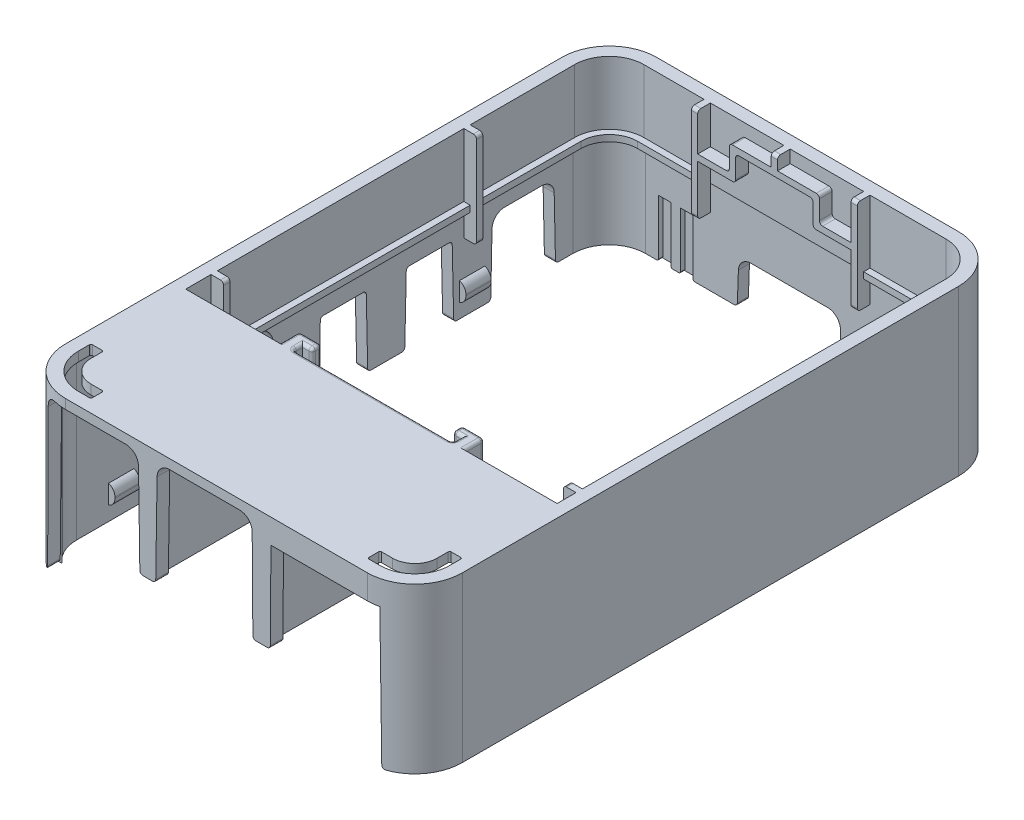
SolidWorks part; units mm, degrees
ref_plane "Plan de face" through (0, 0, 0) normal (0, 0, 1) x (1, 0, 0)
ref_plane "Plan de dessus" through (0, 0, 0) normal (0, 1, 0) x (1, 0, 0)
ref_plane "Plan de droite" through (0, 0, 0) normal (1, 0, 0) x (0, 0, -1)
sketch "Esquisse1" plane through (0, 0, 0) normal (0, 1, 0) x (1, 0, 0)
  line L1 (-31.375, 46.75) -> (31.375, 46.75)
  line L2 (-31.375, 46.75) -> (-31.375, -46.75)
  line L3 (-31.375, -46.75) -> (31.375, -46.75)
  line L4 (31.375, 46.75) -> (31.375, -46.75)
  line L5 (-31.375, 46.75) -> (31.375, -46.75) construction
  line L6 (-31.375, -46.75) -> (31.375, 46.75) construction
  point P0 (0, 0)
  dimension "D1" = 62.75
  dimension "D2" = 93.5
extrude "Contour_de_matiere" add sketch "Esquisse1" along normal blind 26
fillet "Arrondissement_des_coins" radius 7.5 4 edges at (-31.375, 13, -46.75) (31.375, 13, -46.75) (31.375, 13, 46.75) (-31.375, 13, 46.75)
sketch "Esquisse2" plane through (0, 26, 0) normal (0, 1, 0) x (1, 0, 0)
  line L0 (-29.375, -22.25) -> (29.375, -22.25)
  line L4 (-23.875, -46.75) -> (23.875, -46.75) construction
  line L8 (-23.875, 44.75) -> (23.875, 44.75)
  line L9 (-29.375, 39.25) -> (-29.375, -22.25)
  line L10 (29.375, 39.25) -> (29.375, -22.25)
  line L11 (31.375, -39.25) -> (31.375, 39.25) construction
  line L12 (-31.375, 39.25) -> (-31.375, -39.25) construction
  line L13 (23.875, 46.75) -> (-23.875, 46.75) construction
  arc A2 (-29.375, 39.25) -> (-23.875, 44.75) centre (-23.875, 39.25) cw
  arc A3 (23.875, 44.75) -> (29.375, 39.25) centre (23.875, 39.25) cw
  dimension "D4" = 24.5
  dimension "D5" = 5.5
  dimension "D6" = 5.5
  dimension "D1" = 2
  dimension "D2" = 2
  dimension "D3" = 2
extrude "Creusage_du_trou_central" cut sketch "Esquisse2" against normal up to next
ref_plane "Plan_pour_rebord_interieur" through (0, 15, 0) normal (0, 1, 0) x (1, 0, 0)
sketch "Esquisse4" plane through (0, 15, 0) normal (0, 1, 0) x (1, 0, 0)
  line L0 (-28.375, -22.25) -> (-31.375, -22.25)
  line L1 (-29.375, -22.25) -> (29.375, -22.25) construction
  line L2 (-31.375, 39.25) -> (-31.375, -39.25) construction
  line L3 (-31.375, -22.25) -> (-31.375, 39.25)
  line L4 (-23.875, 46.75) -> (23.875, 46.75)
  line L5 (31.375, 39.25) -> (31.375, -22.25)
  line L6 (31.375, -39.25) -> (31.375, 39.25) construction
  line L7 (31.375, -22.25) -> (28.375, -22.25)
  line L8 (28.375, -22.25) -> (28.375, 39.25)
  line L9 (-28.375, -22.25) -> (-28.375, 39.25)
  line L10 (-23.875, 43.75) -> (23.875, 43.75)
  line L11 (-29.375, 39.25) -> (-29.375, -22.25) construction
  line L12 (29.375, -22.25) -> (29.375, 39.25) construction
  line L13 (23.875, 44.75) -> (-23.875, 44.75) construction
  arc A0 (-31.375, 39.25) -> (-23.875, 46.75) centre (-23.875, 39.25) cw
  arc A1 (23.875, 46.75) -> (31.375, 39.25) centre (23.875, 39.25) cw
  arc A2 (-28.375, 39.25) -> (-23.875, 43.75) centre (-23.875, 39.25) cw
  arc A3 (23.875, 43.75) -> (28.375, 39.25) centre (23.875, 39.25) cw
  dimension "D4" = 4.5
  dimension "D5" = 4.5
  dimension "D1" = 1
  dimension "D2" = 1
  dimension "D3" = 1
extrude "Rebord_interieux" add sketch "Esquisse4" along normal blind 1
sketch "Esquisse5" plane through (0, 26, 0) normal (0, 1, 0) x (1, 0, 0)
  line L0 (-31.375, 39.25) -> (-31.375, -39.25) construction
  line L1 (-31.375, -18.25) -> (-27.375, -18.25)
  line L2 (-31.375, -18.25) -> (-31.375, -17.25)
  line L3 (-31.375, -17.25) -> (-27.375, -17.25)
  line L4 (-27.375, -18.25) -> (-27.375, -17.25)
  line L5 (-31.375, -18.25) -> (-27.375, -17.25) construction
  line L6 (-31.375, -17.25) -> (-27.375, -18.25) construction
  line L7 (23.875, 46.75) -> (-23.875, 46.75) construction
  line L8 (31.375, -39.25) -> (31.375, 39.25) construction
  line L9 (31.375, -19.25) -> (27.375, -19.25)
  line L10 (31.375, -19.25) -> (31.375, -18.25)
  line L11 (31.375, -18.25) -> (27.375, -18.25)
  line L12 (27.375, -19.25) -> (27.375, -18.25)
  line L13 (31.375, -19.25) -> (27.375, -18.25) construction
  line L14 (31.375, -18.25) -> (27.375, -19.25) construction
  line L15 (10.875, 46.75) -> (11.875, 46.75)
  line L16 (-29.375, -22.25) -> (29.375, -22.25) construction
  line L17 (-31.375, 21.75) -> (-27.375, 21.75)
  line L18 (-31.375, 21.75) -> (-31.375, 22.75)
  line L19 (-31.375, 22.75) -> (-27.375, 22.75)
  line L20 (-27.375, 21.75) -> (-27.375, 22.75)
  line L21 (-31.375, 21.75) -> (-27.375, 22.75) construction
  line L22 (-31.375, 22.75) -> (-27.375, 21.75) construction
  line L23 (28.375, -22.25) -> (29.375, -22.25) construction
  line L24 (10.875, 46.75) -> (10.875, 42.75)
  line L25 (10.875, 42.75) -> (11.875, 42.75)
  line L26 (11.875, 46.75) -> (11.875, 42.75)
  line L27 (10.875, 46.75) -> (11.875, 42.75) construction
  line L28 (10.875, 42.75) -> (11.875, 46.75) construction
  line L30 (-14.375, 46.75) -> (-13.375, 46.75)
  line L31 (-14.375, 46.75) -> (-14.375, 42.75)
  line L32 (-14.375, 42.75) -> (-13.375, 42.75)
  line L33 (-13.375, 46.75) -> (-13.375, 42.75)
  line L34 (-14.375, 46.75) -> (-13.375, 42.75) construction
  line L35 (-14.375, 42.75) -> (-13.375, 46.75) construction
  point P4 (-29.375, -17.75)
  point P13 (29.375, -18.75)
  point P22 (-29.375, 22.25)
  point P27 (11.375, 44.75)
  point P34 (-13.875, 44.75)
  dimension "D1" = 1
  dimension "D2" = 1
  dimension "D3" = 1
  dimension "D4" = 4
  dimension "D5" = 3
  dimension "D6" = 39
  dimension "D7" = 4
  dimension "D8" = 4
  dimension "D9" = 4
  dimension "D10" = 1
  dimension "D11" = 1
  dimension "D12" = 18
  dimension "D13" = 20.5
extrude "Rebord_verticaux" add sketch "Esquisse5" against normal blind 15
sketch "Esquisse6" plane through (0, 0, -43.75) normal (0, 0, 1) x (1, 0, 0)
  line L0 (34.5125, 15) -> (-34.5125, 15) construction
  line L1 (-13.375, 16) -> (10.875, 16)
  line L2 (-13.375, 16) -> (-13.375, 15)
  line L3 (-13.375, 15) -> (10.875, 15)
  line L4 (10.875, 16) -> (10.875, 15)
  line L5 (-13.375, 16) -> (10.875, 15) construction
  line L6 (-13.375, 15) -> (10.875, 16) construction
  line L7 (10.875, 11) -> (10.875, 26) construction
  point P4 (-1.25, 15.5)
extrude "Trou_de_detail" cut sketch "Esquisse6" against normal blind 1
sketch "Esquisse7" plane through (0, 0, -44.75) normal (0, 0, 1) x (1, 0, 0)
  line L0 (-13.375, 26) -> (-13.375, 11) construction
  line L1 (-13.375, 20) -> (-7.375, 20)
  line L2 (-13.375, 20) -> (-13.375, 19)
  line L3 (-13.375, 19) -> (-7.375, 19)
  line L4 (-7.375, 20) -> (-7.375, 19)
  line L5 (-13.375, 20) -> (-7.375, 19) construction
  line L6 (-13.375, 19) -> (-7.375, 20) construction
  line L7 (10.875, 11) -> (10.875, 26) construction
  line L8 (10.875, 19) -> (4.875, 19)
  line L9 (10.875, 19) -> (10.875, 20)
  line L10 (10.875, 20) -> (4.875, 20)
  line L11 (4.875, 19) -> (4.875, 20)
  line L12 (10.875, 19) -> (4.875, 20) construction
  line L13 (10.875, 20) -> (4.875, 19) construction
  line L14 (10.875, 26) -> (-13.375, 26) construction
  line L15 (11.875, 11) -> (11.875, 26) construction
  line L16 (-8.375, 24) -> (5.875, 24)
  line L17 (-8.375, 24) -> (-8.375, 23)
  line L18 (-8.375, 23) -> (5.875, 23)
  line L19 (5.875, 24) -> (5.875, 23)
  line L20 (-8.375, 24) -> (5.875, 23) construction
  line L21 (-8.375, 23) -> (5.875, 24) construction
  line L22 (-8.375, 24) -> (-7.375, 24)
  line L23 (-8.375, 24) -> (-8.375, 19)
  line L24 (-8.375, 19) -> (-7.375, 19)
  line L25 (-7.375, 24) -> (-7.375, 19)
  line L26 (-8.375, 24) -> (-7.375, 19) construction
  line L27 (-8.375, 19) -> (-7.375, 24) construction
  line L28 (5.875, 24) -> (4.875, 24)
  line L29 (5.875, 24) -> (5.875, 19)
  line L30 (5.875, 19) -> (4.875, 19)
  line L31 (4.875, 24) -> (4.875, 19)
  line L32 (5.875, 24) -> (4.875, 19) construction
  line L33 (5.875, 19) -> (4.875, 24) construction
  line L34 (-1.75, 26) -> (-0.75, 26)
  line L35 (-1.75, 26) -> (-1.75, 23)
  line L36 (-1.75, 23) -> (-0.75, 23)
  line L37 (-0.75, 26) -> (-0.75, 23)
  line L38 (-1.75, 26) -> (-0.75, 23) construction
  line L39 (-1.75, 23) -> (-0.75, 26) construction
  line L41 (11.875, 26) -> (11.875, 16) construction
  line L42 (-14.375, 16) -> (-14.375, 26) construction
  point P4 (-10.375, 19.5)
  point P11 (7.875, 19.5)
  point P20 (-1.25, 23.5)
  point P24 (-7.875, 21.5)
  point P27 (5.375, 21.5)
  point P31 (-1.25, 24.5)
  line M22 (10.875, 11) -> (10.875, 26)
  line M23 (10.875, 26) -> (-13.375, 26)
  line M24 (-13.375, 26) -> (-13.375, 11)
  dimension "D1" = 7
  dimension "D2" = 7
  dimension "D3" = 1
  dimension "D4" = 1
  dimension "D5" = 7
  dimension "D6" = 7
  dimension "D7" = 1
  dimension "D8" = 1
  dimension "D9" = 5
  dimension "D10" = 1
  dimension "D11" = 1
  dimension "D12" = 13.625
extrude "Fancy_truc_devant" add sketch "Esquisse7" along normal blind 2 contours L23 L1 L3 M24 | L1 L23 L3 L4 | L25 L18 L23 L1 | L25 L16 L17 L18 | L35 L16 L25 L18 | L37 L16 L35 L18 | L37 L35 L16 M23 | L16 L37 L18 L31 | L16 L31 L18 L19 | L18 L31 L10 L29 | L29 L10 L11 L8 | L10 L29 L8 M22
sketch "Esquisse9" plane through (0, 0, 0) normal (0, -1, 0) x (1, 0, 0)
  line L0 (-29.375, 22.25) -> (-29.375, 39.25)
  line L1 (-29.375, 22.25) -> (29.375, 22.25)
  line L2 (29.375, 22.25) -> (29.375, 39.25)
  line L3 (-23.875, 44.75) -> (23.875, 44.75)
  arc A0 (-29.375, 39.25) -> (-23.875, 44.75) centre (-23.875, 39.25) cw
  arc A1 (29.375, 39.25) -> (23.875, 44.75) centre (23.875, 39.25) ccw
  dimension "D1" = 5.5
  dimension "D4" = 5.5
  dimension "D2" = 2
  dimension "D3" = 2
extrude "Trou_de_dessous" cut sketch "Esquisse9" against normal offset from surface (24.5 mm away) 1.5 up to face at (-4.2833, 26, -19.7926)
sketch "Esquisse8" plane through (0, 26, 0) normal (0, 1, 0) x (1, 0, 0)
  line L0 (-14.625, -19) -> (-14.625, -23)
  line L1 (-14.625, -23) -> (14.625, -23)
  line L2 (14.625, -23) -> (14.625, -19)
  line L3 (14.625, -19) -> (11.125, -19)
  line L4 (11.125, -19) -> (11.125, -20.5)
  line L5 (11.125, -20.5) -> (12.625, -20.5)
  line L6 (12.625, -20.5) -> (12.625, -22)
  line L8 (12.625, -22) -> (-12.625, -22)
  line L9 (-12.625, -22) -> (-12.625, -20.5)
  line L10 (-12.625, -20.5) -> (-11.125, -20.5)
  line L11 (-11.125, -20.5) -> (-11.125, -19)
  line L12 (-11.125, -19) -> (-14.625, -19)
  line L13 (29.375, -22.25) -> (29.375, -19.25) construction
  line L14 (-29.375, -22.25) -> (29.375, -22.25) construction
  point P17 (11.875, -20.5)
  dimension "D1" = 14.75
  dimension "D2" = 14.75
  dimension "D3" = 2
  dimension "D4" = 2
  dimension "D5" = 1.5
  dimension "D6" = 1.5
  dimension "D7" = 0.25
  dimension "D8" = 1.5
  dimension "D9" = 1.5
  dimension "D10" = 3.5
  dimension "D11" = 3.5
  dimension "D12" = 1
extrude "Extrusion_de_fils" add sketch "Esquisse8" against normal blind 4.5
sketch "Esquisse10" plane through (0, 24.5, 0) normal (0, -1, 0) x (1, 0, 0)
  line L0 (29.375, 22.25) -> (29.375, 39.25) construction
  line L1 (-29.375, 22.25) -> (29.375, 22.25)
  line L2 (-29.375, 22.25) -> (-29.375, 23)
  line L3 (-29.375, 23) -> (29.375, 23)
  line L4 (29.375, 22.25) -> (29.375, 23)
  line L5 (-29.375, 22.25) -> (29.375, 23) construction
  line L6 (-29.375, 23) -> (29.375, 22.25) construction
  point P4 (0, 22.625)
  dimension "D1" = 0.75
extrude "Rebord_contour_top" add sketch "Esquisse10" along normal blind 1
sketch "Esquisse11" plane through (29.375, 0, 0) normal (-1, 0, 0) x (0, 0, 1)
  line L1 (22.25, 15) -> (23, 15)
  line L2 (22.25, 15) -> (22.25, 24.5)
  line L3 (22.25, 24.5) -> (23, 24.5)
  line L4 (23, 15) -> (23, 24.5)
  line L5 (22.25, 15) -> (23, 24.5) construction
  line L6 (22.25, 24.5) -> (23, 15) construction
  point P4 (22.625, 19.75)
extrude "Connexion_un_cote" add sketch "Esquisse11" along normal blind 1
mirror "Symetrie_de_connexion" about plane through (0, 0, 0) normal (1, 0, 0) of "Connexion_un_cote"
sketch "Esquisse12" plane through (0, 15, 0) normal (0, 1, 0) x (1, 0, 0)
  line L0 (-29.375, -39.25) -> (-29.375, 39.25)
  line L1 (-23.875, -44.75) -> (23.875, -44.75)
  line L2 (29.375, 39.25) -> (29.375, -39.25)
  line L3 (-23.875, 44.75) -> (23.875, 44.75)
  line L4 (-29.625, -39.25) -> (-29.625, 39.25)
  line L5 (-23.875, 45) -> (23.875, 45)
  line L6 (29.625, 39.25) -> (29.625, -39.25)
  line L7 (23.875, -45) -> (-23.875, -45)
  line L8 (-31.375, 39.25) -> (-31.375, -39.25) construction
  line L9 (-23.875, -46.75) -> (23.875, -46.75) construction
  line L10 (31.375, -39.25) -> (31.375, 39.25) construction
  line L11 (23.875, 46.75) -> (-23.875, 46.75) construction
  arc A0 (-29.375, 39.25) -> (-23.875, 44.75) centre (-23.875, 39.25) cw
  arc A1 (-29.375, -39.25) -> (-23.875, -44.75) centre (-23.875, -39.25) ccw
  arc A2 (23.875, -44.75) -> (29.375, -39.25) centre (23.875, -39.25) ccw
  arc A3 (23.875, 44.75) -> (29.375, 39.25) centre (23.875, 39.25) cw
  arc A4 (23.875, 45) -> (29.625, 39.25) centre (23.875, 39.25) cw
  arc A5 (29.625, -39.25) -> (23.875, -45) centre (23.875, -39.25) cw
  arc A6 (-29.625, -39.25) -> (-23.875, -45) centre (-23.875, -39.25) ccw
  arc A7 (-23.875, 45) -> (-29.625, 39.25) centre (-23.875, 39.25) ccw
  dimension "D1" = 1.75
  dimension "D2" = 1.75
  dimension "D3" = 1.75
  dimension "D4" = 1.75
extrude "Enlèv. mat.-Extru.1" cut sketch "Esquisse12" against normal up to next
sketch "Esquisse14" plane through (0, 24.5, 0) normal (0, -1, 0) x (1, 0, 0)
  line L0 (29.625, 23) -> (29.625, 39.25)
  line L1 (29.625, 23) -> (-29.625, 23)
  line L2 (-29.625, 23) -> (-29.625, 39.25)
  line L3 (-23.875, 45) -> (23.875, 45)
  line L4 (-23.875, 46.75) -> (23.875, 46.75) construction
  line L5 (-31.375, -39.25) -> (-31.375, 39.25) construction
  line L6 (31.375, 39.25) -> (31.375, -39.25) construction
  line L7 (-29.375, 23) -> (29.375, 23) construction
  arc A0 (23.875, 45) -> (29.625, 39.25) centre (23.875, 39.25) cw
  arc A1 (-29.625, 39.25) -> (-23.875, 45) centre (-23.875, 39.25) cw
  dimension "D1" = 1.75
  dimension "D2" = 1.75
  dimension "D3" = 1.75
extrude "Enlèv. mat.-Extru.2" cut sketch "Esquisse14" along normal up to next
sketch "Esquisse15" plane through (0, 0, 0) normal (0, -1, 0) x (-1, 0, 0)
  line L0 (27.625, -45.7452) -> (27.625, -43.6089)
  line L1 (-8.125, -46.75) -> (-8.125, -45)
  line L2 (23.875, -46.75) -> (-23.875, -46.75) construction
  line L3 (-23.875, -45) -> (23.875, -45) construction
  line L4 (-8.125, -46.75) -> (23.875, -46.75)
  line L5 (-8.125, -45) -> (23.875, -45)
  line L6 (31.375, 39.25) -> (31.375, -39.25) construction
  arc A0 (23.875, -46.75) -> (31.375, -39.25) centre (23.875, -39.25) ccw construction
  arc A1 (23.875, -45) -> (29.625, -39.25) centre (23.875, -39.25) ccw construction
  arc A2 (27.625, -43.6089) -> (23.875, -45) centre (23.875, -39.25) cw
  arc A3 (23.875, -46.75) -> (27.625, -45.7452) centre (23.875, -39.25) ccw
  dimension "D1" = 3.75
  dimension "D2" = 39.5
extrude "Enlèv. mat.-Extru.3" cut sketch "Esquisse15" against normal up to surface (24.5 mm away) up to face at (0, 24.5, 36.147)
sketch "Esquisse16" plane through (0, 0, 0) normal (0, -1, 0) x (-1, 0, 0)
  line L0 (-25.625, -44.7272) -> (-25.625, -46.543)
  line L1 (-8.125, -45) -> (-8.125, -46.75)
  line L2 (-8.125, -45) -> (-23.875, -45)
  line L3 (-23.875, -45) -> (-8.125, -45) construction
  line L4 (-8.125, -46.75) -> (-23.875, -46.75)
  line L5 (-31.375, -39.25) -> (-31.375, 39.25) construction
  arc A0 (-29.625, -39.25) -> (-23.875, -45) centre (-23.875, -39.25) ccw construction
  arc A1 (-31.375, -39.25) -> (-23.875, -46.75) centre (-23.875, -39.25) ccw construction
  arc A2 (-23.875, -46.75) -> (-25.625, -46.543) centre (-23.875, -39.25) cw
  arc A3 (-23.875, -45) -> (-25.625, -44.7272) centre (-23.875, -39.25) cw
  dimension "D1" = 5.75
extrude "Enlèv. mat.-Extru.4" cut sketch "Esquisse16" against normal offset from surface (22.15 mm away) 3.85
sketch "Esquisse17" plane through (0, 0, 46.75) normal (0, 0, 1) x (1, 0, 0)
  line L0 (-12.375, 24.5) -> (-12.125, 7.85)
  line L1 (8.125, 24.5) -> (-23.875, 24.5) construction
  line L2 (-12.125, 7.85) -> (-9.625, 7.85)
  line L3 (-9.625, 7.85) -> (-9.375, 24.5)
  line L4 (-9.375, 24.5) -> (-12.375, 24.5)
  line L5 (-29.625, 24.5) -> (29.625, 24.5) construction
  line L7 (-23.875, 26) -> (23.875, 26) construction
  line L8 (-31.375, 0) -> (-31.375, 26) construction
  line L9 (5.625, 24.5) -> (8.625, 24.5)
  line L10 (8.625, 24.5) -> (8.5, 7.85)
  line L11 (8.5, 7.85) -> (5.75, 7.85)
  line L12 (5.75, 7.85) -> (5.625, 24.5)
  point P5 (-10.875, 7.85)
  point P7 (-10.875, 24.5)
  point P8 (7.125, 24.5)
  point P19 (7.125, 7.85)
  dimension "D1" = 3
  dimension "D2" = 2.5
  dimension "D3" = 18.15
  dimension "D4" = 22
  dimension "D5" = 3
  dimension "D6" = 2.75
  dimension "D7" = 18.15
  dimension "D8" = 40
extrude "Boss.-Extru.1" add sketch "Esquisse17" against normal blind 2
sketch "Esquisse18" plane through (0, 24.5, 0) normal (0, -1, 0) x (-1, 0, 0)
  line L0 (11.375, -44.75) -> (10.375, -44.75)
  line L1 (9.375, -44.75) -> (12.375, -44.75) construction
  line L2 (10.375, -44.75) -> (10.375, -28.75)
  line L3 (10.375, -28.75) -> (11.375, -28.75)
  line L4 (11.375, -28.75) -> (11.375, -44.75)
  line L5 (-6.625, -44.75) -> (-7.625, -44.75)
  line L6 (-8.625, -44.75) -> (-5.625, -44.75) construction
  line L7 (-7.625, -44.75) -> (-7.625, -28.75)
  line L8 (-7.625, -28.75) -> (-6.625, -28.75)
  line L9 (-6.625, -28.75) -> (-6.625, -44.75)
  line L10 (-5.625, -46.75) -> (9.375, -46.75) construction
  point P14 (10.875, -44.75)
  point P15 (10.875, -44.75)
  point P16 (-7.125, -44.75)
  point P17 (-7.125, -44.75)
  dimension "D1" = 1
  dimension "D2" = 1
  dimension "D3" = 18
  dimension "D4" = 18
extrude "Boss.-Extru.2" add sketch "Esquisse18" along normal offset from surface (16.5 mm away) 0.15 up to face at (7.125, 7.85, 45.75)
sketch "Esquisse22" plane through (0, 24.5, 0) normal (0, -1, 0) x (-1, 0, 0)
  line L0 (10.375, -28.75) -> (11.375, -28.75)
  line L1 (11.375, -28.75) -> (11.375, -23)
  line L2 (29.625, -23) -> (-29.625, -23) construction
  line L3 (11.375, -23) -> (10.375, -23)
  line L4 (10.375, -23) -> (10.375, -28.75)
  line L5 (-6.625, -28.75) -> (-7.625, -28.75)
  line L6 (-7.625, -28.75) -> (-7.625, -23)
  line L7 (-7.625, -23) -> (-6.625, -23)
  line L8 (-6.625, -23) -> (-6.625, -28.75)
extrude "Boss.-Extru.3" add sketch "Esquisse22" along normal up to surface (3 mm away) up to face at (0, 21.5, 20.6667)
sketch "Esquisse24" plane through (-11.375, 0, 0) normal (-1, 0, 0) x (0, 0, 1)
  line L0 (28.75, 13) -> (23, 21.5)
  line L1 (28.75, 8) -> (28.75, 21.5) construction
  dimension "D1" = 5
rib "Nervure1" sketch "Esquisse24" sketch "Esquisse24" thickness 1 extrusion direction parallel to sketch draft on no parameters "D1"=1
sketch "Esquisse25" plane through (6.625, 0, 0) normal (-1, 0, 0) x (0, 0, 1)
  line L0 (28.75, 13) -> (23, 21.5)
  line L1 (28.75, 8) -> (28.75, 21.5) construction
  dimension "D1" = 5
rib "Nervure2" sketch "Esquisse25" sketch "Esquisse25" thickness 1 extrusion direction parallel to sketch draft on no parameters "D1"=1
sketch "Esquisse27" plane through (0, 0, -46.75) normal (0, 0, -1) x (-1, 0, 0)
  line L0 (-7.125, 0) -> (9.375, 0)
  line L1 (-23.875, 0) -> (23.875, 0) construction
  line L2 (9.375, 0) -> (9.125, 7)
  line L3 (9.125, 7) -> (-6.875, 7)
  line L4 (-6.875, 7) -> (-7.125, 0)
  line L5 (-23.875, 26) -> (23.875, 26) construction
  point P4 (1.125, 7)
  point P7 (1.125, 0)
  dimension "D1" = 16.5
  dimension "D2" = 16
  dimension "D3" = 19
  dimension "D4" = 22
extrude "Enlèv. mat.-Extru.5" cut sketch "Esquisse27" against normal up to next
sketch "Esquisse28" plane through (-31.375, 0, 0) normal (-1, 0, 0) x (0, 0, 1)
  line L0 (-36.5, 0) -> (-26.25, 0)
  line L1 (-39.25, 0) -> (39.25, 0) construction
  line L2 (-26.25, 0) -> (-26.5, 11.75)
  line L3 (-26.5, 11.75) -> (-36.25, 11.75)
  line L4 (-36.25, 11.75) -> (-36.5, 0)
  line L5 (-39.25, 26) -> (39.25, 26) construction
  line L6 (-20.4, 0) -> (-12.65, 0)
  line L7 (-12.65, 0) -> (-12.9, 11.25)
  line L8 (-12.9, 11.25) -> (-20.15, 11.25)
  line L9 (-20.15, 11.25) -> (-20.4, 0)
  line L10 (-6.8, 0) -> (-6.55, 11.25)
  line L11 (-6.55, 11.25) -> (0.7, 11.25)
  line L12 (0.7, 11.25) -> (0.95, 0)
  line L13 (0.95, 0) -> (-6.8, 0)
  line L14 (7.95, 0) -> (15.2, 0)
  line L15 (7.95, 0) -> (8.075, 11)
  line L16 (15.075, 11) -> (15.2, 0)
  arc A0 (8.075, 11) -> (15.075, 11) centre (11.575, 11) cw
  point P4 (-31.375, 11.75)
  point P7 (-31.375, 0)
  point P13 (-16.525, 11.25)
  point P16 (-16.525, 0)
  point P19 (-2.925, 0)
  point P22 (-2.925, 11.25)
  point P25 (11.575, 14.5)
  point P29 (11.575, 0)
  dimension "D1" = 9.75
  dimension "D2" = 10.25
  dimension "D3" = 14.25
  dimension "D4" = 10.25
  dimension "D5" = 7.25
  dimension "D6" = 7.75
  dimension "D7" = 5.85
  dimension "D8" = 7.25
  dimension "D9" = 7.75
  dimension "D10" = 14.75
  dimension "D11" = 5.85
  dimension "D12" = 7
  dimension "D13" = 7.25
  dimension "D14" = 11.5
  dimension "D15" = 7
  dimension "D16" = 3.5
extrude "Enlèv. mat.-Extru.6" cut sketch "Esquisse28" against normal up to next
ref_plane "Plan3" through (0, 0, 46.75) normal (0, 0, 1) x (1, 0, 0)
sketch "Esquisse29" plane through (0, 0, 46.75) normal (0, 0, 1) x (1, 0, 0)
  line L0 (-27.625, 0) -> (-27.625, 24.5)
  line L1 (-27.625, 24.5) -> (-27.875, 0)
  line L2 (-31.375, 0) -> (-27.625, 0) construction
  line L3 (-27.875, 0) -> (-27.625, 0)
  line L4 (25.625, 22.15) -> (25.625, 0)
  line L5 (25.625, 0) -> (25.875, 0)
  line L6 (25.625, 0) -> (31.375, 0) construction
  line L7 (25.875, 0) -> (25.625, 22.15)
  line L8 (-27.625, 24.5) -> (-23.875, 24.5) construction
  dimension "D1" = 0.25
  dimension "D2" = 0.25
extrude "Enlèv. mat.-Extru.7" cut sketch "Esquisse29" against normal up to vertex (3.1411 mm away)
sketch "Esquisse30" plane through (0, 26, 0) normal (0, 1, 0) x (1, 0, 0)
  line L9 (-21.875, -44.75) -> (-21.875, -42.75)
  line L10 (-29.375, -37.25) -> (-27.375, -37.25)
  line L11 (-23.875, -46.75) -> (23.875, -46.75) construction
  line L12 (-31.375, 39.25) -> (-31.375, -39.25) construction
  line L13 (-29.375, -39.25) -> (-29.375, -37.25)
  line L14 (-23.875, -44.75) -> (-21.875, -44.75)
  line L15 (-27.375, -37.25) -> (-27.375, -39.25)
  line L16 (-21.875, -42.75) -> (-23.875, -42.75)
  arc A2 (-23.875, -44.75) -> (-29.375, -39.25) centre (-23.875, -39.25) cw
  arc A3 (-23.875, -42.75) -> (-27.375, -39.25) centre (-23.875, -39.25) cw
  dimension "D1" = 2
  dimension "D2" = 2
  dimension "D3" = 9.5
  dimension "D4" = 9.5
  dimension "D5" = 2
  dimension "D6" = 2
extrude "Enlèv. mat.-Extru.9" cut sketch "Esquisse30" against normal up to next
mirror "Symétrie2" about plane through (0, 0, 0) normal (1, 0, 0) of "Enlèv. mat.-Extru.9"
fillet "Congé1" radius 0.5 75 edges at (-27.375, 26, 17.75) (-27.375, 11, 17.75) (11.375, 26, -42.75) (11.375, 11, -42.75) (27.375, 26, 18.75) (27.375, 11, 18.75) (-27.375, 26, -22.25) (-27.375, 11, -22.25) (-13.875, 26, -42.75) (-13.875, 11, -42.75) (-7.375, 19, -43.75) (-7.375, 23, -43.75) (4.875, 23, -43.75) (4.875, 19, -43.75) (5.875, 20, -43.75) (5.875, 24, -43.75) (-8.375, 24, -43.75) (-8.375, 20, -43.75) (-1.25, 26, -42.75) (14.625, 26, 20.625) (12.875, 26, 19) (11.125, 26, 19.75) (11.875, 26, 20.5) (12.625, 26, 21.25) (0, 26, 22) (-12.625, 26, 21.25) (-11.875, 26, 20.5) (-11.125, 26, 19.75) (-12.875, 26, 19) (-14.625, 26, 20.625) (14.625, 21.5, 21) (14.625, 23.75, 19) (-13, 21.5, 23) (-14.625, 21.5, 21) (-12.875, 21.5, 19) (-14.625, 23.75, 19) (-11.125, 21.5, 19.75) (-11.125, 23.75, 19) (-11.875, 21.5, 20.5) (-11.125, 23.75, 20.5) (-12.625, 21.5, 21.25) (0, 21.5, 22) (-12.625, 23.75, 22) (12.625, 21.5, 21.25) (12.625, 23.75, 22) (11.875, 21.5, 20.5) (11.125, 21.5, 19.75) (11.125, 23.75, 20.5) (12.875, 21.5, 19) (11.125, 23.75, 19) (-9.625, 7.85, 45.75) (-12.125, 7.85, 45.75) (8.5, 7.85, 45.75) (5.75, 7.85, 45.75) (-10.875, 8, 28.75) (7.125, 8, 28.75) (11.125, 21.5, 23) (7.125, 0, -45.875) (-9.375, 0, -45.875) (-30.5, 0, -36.5) (-30.5, 0, -26.25) (-30.5, 0, -20.4) (-30.5, 11.25, -20.15) (-30.5, 11.25, -12.9) (-30.5, 0, -12.65) (-30.5, 0, 0.95) (-30.5, 0, -6.8) (-30.5, 11.25, -6.55) (-30.5, 11.25, 0.7) (-30.5, 0, 7.95) (-30.5, 0, 15.2) (-27.875, 0, 44.6016) (25.7503, 11.0504, 46.5118) (25.7505, 11.0311, 44.6855) (25.875, 0, 45.5597)
sketch "Esquisse31" plane through (0, 0, 0) normal (0, -1, 0) x (-1, 0, 0)
  line L0 (23.875, 45) -> (9.8575, 45) construction
  line L1 (16.3578, 45) -> (18.3578, 45)
  line L2 (16.3578, 45) -> (16.3578, 45.75)
  line L3 (16.3578, 45.75) -> (18.3578, 45.75)
  line L4 (18.3578, 45) -> (18.3578, 45.75)
  line L5 (16.3578, 45) -> (18.3578, 45.75) construction
  line L6 (16.3578, 45.75) -> (18.3578, 45) construction
  line L7 (-23.875, 45) -> (23.875, 45) construction
  line L8 (19.8578, 45) -> (21.8578, 45)
  line L9 (19.8578, 45) -> (19.8578, 45.75)
  line L10 (19.8578, 45.75) -> (21.8578, 45.75)
  line L11 (21.8578, 45) -> (21.8578, 45.75)
  line L12 (19.8578, 45) -> (21.8578, 45.75) construction
  line L13 (19.8578, 45.75) -> (21.8578, 45) construction
  line L14 (9.8575, 46.75) -> (23.875, 46.75) construction
  point P4 (17.3578, 45.375)
  point P11 (20.8578, 45.375)
  dimension "D1" = 2
  dimension "D2" = 2
  dimension "D3" = 1
  dimension "D4" = 1
  dimension "D5" = 1.5
  dimension "D6" = 7
extrude "Enlèv. mat.-Extru.10" cut sketch "Esquisse31" against normal blind 9
fillet "Congé2" radius 2 8 edges at (6.875, 7, -45.875) (-9.125, 7, -45.875) (5.625, 24.5, 45.75) (-9.375, 24.5, 45.75) (-12.375, 24.5, 45.75) (-27.625, 24.5, 44.677) (-30.5, 11.75, -26.5) (-30.5, 11.75, -36.25)
fillet "Congé3" radius 1 4 edges at (29, 15, 23) (-29, 15, 23) (-28.875, 16, 22.25) (28.875, 16, 22.25)
fillet "Congé4" radius 3.5 2 edges at (28.375, 23.5, 22.625) (-28.375, 23.5, 22.625)
sketch "Esquisse32" plane through (-29.625, 0, 0) normal (1, 0, 0) x (0, 0, -1)
  line L0 (20.889, 0) -> (25.7605, 0) construction
  line L1 (21.3248, 5.25) -> (25.3248, 5.25)
  line L2 (21.3248, 5.25) -> (21.3248, 2.25)
  line L3 (21.3248, 2.25) -> (25.3248, 2.25)
  line L4 (25.3248, 5.25) -> (25.3248, 2.25)
  line L5 (21.3248, 5.25) -> (25.3248, 2.25) construction
  line L6 (21.3248, 2.25) -> (25.3248, 5.25) construction
  line L7 (-39.25, 0) -> (-15.6944, 0) construction
  line L8 (-34.1944, 5.25) -> (-30.1944, 5.25)
  line L9 (-34.1944, 5.25) -> (-34.1944, 2.25)
  line L10 (-34.1944, 2.25) -> (-30.1944, 2.25)
  line L11 (-30.1944, 5.25) -> (-30.1944, 2.25)
  line L12 (-34.1944, 5.25) -> (-30.1944, 2.25) construction
  line L13 (-34.1944, 2.25) -> (-30.1944, 5.25) construction
  point P4 (23.3248, 3.75)
  point P8 (23.3248, 0)
  point P13 (-32.1944, 3.75)
  dimension "D1" = 4
  dimension "D2" = 3
  dimension "D3" = 5.25
  dimension "D4" = 3
  dimension "D5" = 4
  dimension "D6" = 19
  dimension "D7" = 5.25
extrude "Boss.-Extru.4" add sketch "Esquisse32" along normal blind 1
fillet "Congé5" radius 1.5 4 edges at (-28.625, 5.25, -23.3248) (-28.625, 2.25, -23.3248) (-28.625, 5.25, 32.1944) (-28.625, 2.25, 32.1944)
mirror "Symétrie4" about plane through (0, 0, 0) normal (1, 0, 0) of "Boss.-Extru.4", "Congé5"
fillet "Congé6" radius 0.25 12 edges at (21.875, 25.25, 44.75) (29.375, 25.25, 37.25) (27.375, 25.25, 37.25) (21.875, 25.25, 42.75) (-21.875, 25.25, 44.75) (-21.875, 25.25, 42.75) (-27.375, 25.25, 37.25) (-29.375, 25.25, 37.25) (-16.3578, 0, -45.375) (-19.8578, 0, -45.375) (-21.8578, 0, -45.375) (-18.3578, 0, -45.375)
equation "\"m\"=2.55704"
